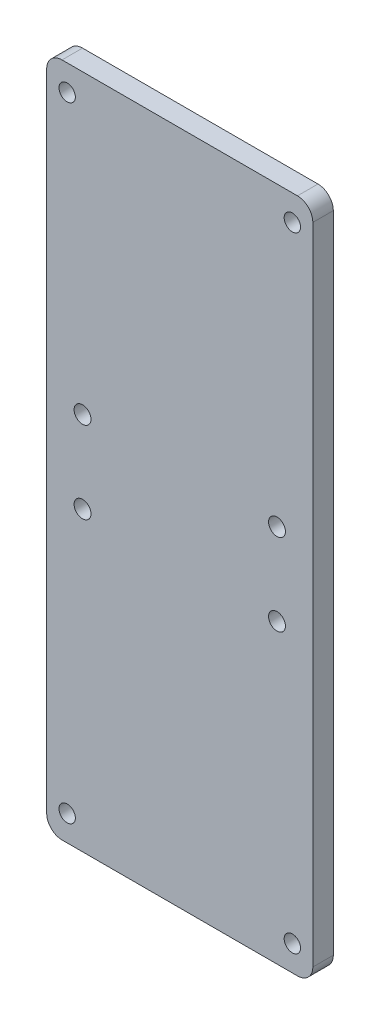
SolidWorks part; units mm, degrees
material "Acrylic (Medium-high impact)"
ref_plane "Front Plane" through (0, 0, 0) normal (0, 0, 1) x (1, 0, 0)
ref_plane "Top Plane" through (0, 0, 0) normal (0, 1, 0) x (1, 0, 0)
ref_plane "Right Plane" through (0, 0, 0) normal (1, 0, 0) x (0, 0, -1)
sketch "Sketch1" plane through (0, 0, 0) normal (0, 0, 1) x (1, 0, 0)
  line L0 (1.25, 61.9364) -> (93.1655, 61.9364) construction
  line L1 (23.2069, 124.9364) -> (23.2069, -1.0636)
  line L2 (26.2069, 127.9364) -> (72.2085, 127.9364)
  line L3 (71.2085, 0.9364) -> (71.2085, -12.0636) construction
  line L4 (26.2069, -4.0636) -> (72.2085, -4.0636)
  line L8 (49.2077, -12.0636) -> (49.2077, 135.9364) construction
  line L20 (75.2085, 124.9364) -> (75.2085, -1.0636)
  circle A0 centre (30.2077, 53.9364) radius 1.65
  circle A1 centre (27.2069, 0.9364) radius 1.6
  arc A2 (26.2069, -4.0636) -> (23.2069, -1.0636) centre (26.2069, -1.0636) cw
  circle A3 centre (68.2077, 69.9364) radius 1.65
  arc A4 (72.2085, -4.0636) -> (75.2085, -1.0636) centre (72.2085, -1.0636) ccw
  circle A5 centre (71.2085, 122.9364) radius 1.6
  arc A6 (72.2085, 127.9364) -> (75.2085, 124.9364) centre (72.2085, 124.9364) cw
  circle A7 centre (71.2085, 0.9364) radius 1.6
  arc A8 (26.2069, 127.9364) -> (23.2069, 124.9364) centre (26.2069, 124.9364) ccw
  circle A9 centre (68.2077, 53.9364) radius 1.65
  circle A10 centre (27.2069, 122.9364) radius 1.6
  circle A11 centre (30.2077, 69.9364) radius 1.65
  point P10 (23.2069, 61.9364)
  point P13 (49.2077, 127.9364)
  point P14 (49.2077, -4.0636)
  point P30 (75.2085, 61.9364)
  dimension "D5" = 22.0008
  dimension "D17" = 3
  dimension "D6" = 3.2
  dimension "D7" = 16
  dimension "D8" = 19
  dimension "D2" = 26.0008
  dimension "D3" = 66
  dimension "D4" = 61
extrude "Boss-Extrude1" add sketch "Sketch1" along normal blind 4
